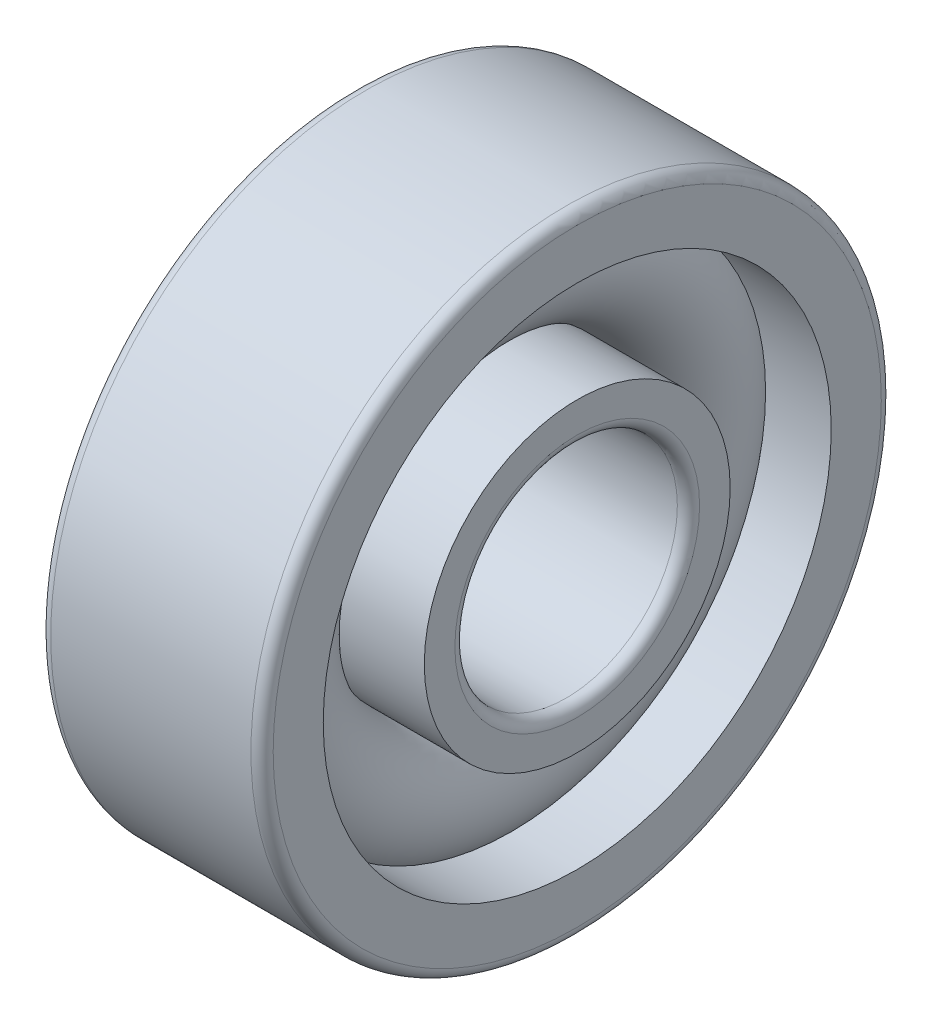
SolidWorks part; units mm, degrees
ref_plane "Plane1" through (0, 0, 0) normal (0, 0, 1) x (1, 0, 0)
ref_plane "Plane2" through (0, 0, 0) normal (0, 1, 0) x (1, 0, 0)
ref_plane "Plane3" through (0, 0, 0) normal (1, 0, 0) x (0, 0, -1)
sketch "Clipboard" plane through (0, 0, 0) normal (0, 0, 1) x (1, 0, 0)
  line L0 (-10, 0) -> (10, 0) construction
  line L1 (0, 0) -> (22.3471, -0.7804)
  line L2 (0, 0) -> (5.7465, 0.2007)
  line L3 (0, 0) -> (22.3471, -0.7804)
  line L4 (0, 0) -> (-22.3573, -0.3902)
sketch "CagSpiSke" plane through (0, 0, 0) normal (0, 0, 1) x (1, 0, 0)
  line L0 (0.4125, 5.475) -> (0.4125, 6.025)
  line L1 (0.4125, 6.025) -> (-0.4125, 6.025)
  line L2 (-0.4125, 6.025) -> (-0.4125, 5.475)
  line L3 (-0.4125, 5.475) -> (0.4125, 5.475)
  line L4 (-20.6375, 0) -> (20.6375, 0) construction
  line L5 (0, 0) -> (0, 23.7692) construction
revolve "CageSpine" add sketch "CagSpiSke" angle 0.001 about L4
ref_axis "Axis1" through (-50, 0, 0) along (1, 0, 0)
sketch "CagBalSke" plane through (0, 0, 0) normal (0, 0, 1) x (1, 0, 0)
  line L0 (-1.815, 5.75) -> (1.815, 5.75)
  line L1 (-1.905, 5.75) -> (1.905, 5.75) construction
  line L2 (-10, 0) -> (10, 0) construction
  line L3 (0, 0) -> (0, 24) construction
  arc A0 (1.815, 5.75) -> (-1.815, 5.75) centre (0, 5.75) cw
revolve "CageBall" [suppressed] add sketch "CagBalSke" angle 360 about L1 reverse direction yes
pattern_circular "CageBalls" [suppressed] count 2 every 180 about axis through (-50, 0, 0) along (1, 0, 0)
sketch "CagTrmODSke" plane through (0, 0, 0) normal (0, 0, 1) x (1, 0, 0)
  line L0 (1.816, 6.025) -> (1.816, 7.566)
  line L1 (1.816, 7.566) -> (-1.816, 7.566)
  line L2 (-1.816, 7.566) -> (-1.816, 6.025)
  line L3 (-1.816, 6.025) -> (1.816, 6.025)
  line L4 (-20.6375, 0) -> (20.6375, 0) construction
  line L5 (0, 0) -> (0, 25) construction
revolve "CageTrimOD" [suppressed] cut sketch "CagTrmODSke" angle 360 about L4 reverse direction yes
sketch "CagTrmIDSke" plane through (0, 0, 0) normal (0, 0, 1) x (1, 0, 0)
  line L0 (1.816, 3.936) -> (1.816, 5.475)
  line L1 (1.816, 5.475) -> (-1.816, 5.475)
  line L2 (-1.816, 5.475) -> (-1.816, 3.936)
  line L3 (-1.816, 3.936) -> (1.816, 3.936)
  line L4 (-20.6375, 0) -> (20.6375, 0) construction
  line L5 (0, 0) -> (0, 25) construction
revolve "CageTrimID" [suppressed] cut sketch "CagTrmIDSke" angle 360 about L4 reverse direction yes
sketch "BalSimSke" plane through (0, 0, 0) normal (0, 0, 1) x (1, 0, 0)
  line L0 (-10, 0) -> (10, 0) construction
  line L1 (-10, 5.75) -> (10, 5.75) construction
  line L2 (0, 0) -> (0, 23) construction
  circle A0 centre (0, 5.75) radius 1.65
revolve "BallsSimplified" add sketch "BalSimSke" angle 360 about L0
sketch "BalDetSke" plane through (0, 0, 0) normal (0, 0, 1) x (1, 0, 0)
  line L0 (-1.65, 5.75) -> (1.65, 5.75)
  line L1 (-1.905, 5.75) -> (1.905, 5.75) construction
  line L2 (0, 0) -> (0, 25) construction
  arc A0 (1.65, 5.75) -> (-1.65, 5.75) centre (0, 5.75) cw
revolve "BallDetailed" [suppressed] add sketch "BalDetSke" angle 360 about L1 reverse direction yes
sketch "InnRacSke" plane through (0, 0, 0) normal (0, 0, 1) x (1, 0, 0)
  line L0 (-1.1961, 4.65) -> (-3, 4.65)
  line L1 (-3, 4.65) -> (-3, 3.3)
  line L2 (-2.7, 3) -> (2.7, 3)
  line L3 (3, 3.3) -> (3, 4.125)
  line L4 (0, 4.125) -> (3, 4.125)
  line L5 (-20.6375, 0) -> (20.6375, 0) construction
  line L6 (0, 0) -> (0, 30) construction
  arc A0 (-3, 3.3) -> (-2.7, 3) centre (-2.7, 3.3) ccw
  arc A1 (2.7, 3) -> (3, 3.3) centre (2.7, 3.3) ccw
  arc A2 (0, 4.125) -> (-1.1961, 4.65) centre (0, 5.75) cw
revolve "InnerRace" add sketch "InnRacSke" angle 360 about L5 reverse direction yes
sketch "OutRacSke" plane through (0, 0, 0) normal (0, 0, 1) x (1, 0, 0)
  line L0 (0, 7.375) -> (-3, 7.375)
  line L1 (-3, 7.375) -> (-3, 8.2)
  line L2 (-2.7, 8.5) -> (2.7, 8.5)
  line L3 (3, 8.2) -> (3, 6.85)
  line L4 (3, 6.85) -> (1.1961, 6.85)
  line L5 (-20.6375, 0) -> (20.6375, 0) construction
  line L6 (0, 0) -> (0, 30) construction
  arc A0 (-3, 8.2) -> (-2.7, 8.5) centre (-2.7, 8.2) cw
  arc A1 (2.7, 8.5) -> (3, 8.2) centre (2.7, 8.2) cw
  arc A2 (1.1961, 6.85) -> (0, 7.375) centre (0, 5.75) ccw
revolve "OuterRace" add sketch "OutRacSke" angle 360 about L5 reverse direction yes
pattern_circular "BallsDetailed" [suppressed] count 2 every 180 about axis through (-50, 0, 0) along (1, 0, 0)
equation "\"BallCLRad@Clipboard\" = ( \"OD@OutRacSke\" + \"ID@InnRacSke\" ) / 4"
equation "\"BallCLRad@BalSimSke\" = \"BallCLRad@Clipboard\""
equation "\"BallCLRad@BalDetSke\" = \"BallCLRad@Clipboard\""
equation "\"BallCLRad@InnRacSke\" = \"BallCLRad@Clipboard\""
equation "\"BallCLRad@OutRacSke\" = \"BallCLRad@Clipboard\""
equation "\"Ball_diameter@InnRacSke\" = \"Ball_diameter@BalDetSke\" - 0.05"
equation "\"Ball_diameter@OutRacSke\" = \"Ball_diameter@BalDetSke\" - 0.05"
equation "\"Ball_diameter@BalSimSke\" = \"Ball_diameter@BalDetSke\""
equation "\"Width@OutRacSke\" = \"Width@InnRacSke\""
equation "\"Fillet_radius@OutRacSke\" = \"Fillet_radius@InnRacSke\""
equation "\"Max_count@Clipboard\" = int( 3.14159265 / atn(( \"Ball_diameter@BalDetSke\" / 2) / sqr( \"BallCLRad@Clipboard\"  *  \"BallCLRad@Clipboard\" - ( \"Ball_diameter@BalDetSke\" / 2) *  ( \"Ball_diameter@BalDetSke\" / 2))))"
equation "\"Max_count@Clipboard\" = ((sgn( \"Max_count@Clipboard\" - \"Count@Clipboard\" )-1)*( \"Max_count@Clipboard\" - \"Count@Clipboard\" ))/-2+ \"Count@Clipboard\""
equation "\"Count@BallsDetailed\" = int( \"Show_count@Clipboard\" ) "
equation "\"Count@BallsDetailed\" = ((sgn( \"Count@BallsDetailed\" - \"Max_count@Clipboard\" )-1)*( \"Count@BallsDetailed\" - \"Max_count@Clipboard\" ))/-2+ \"Max_count@Clipboard\""
equation "\"Count@BallsDetailed\" = ((sgn( \"Count@BallsDetailed\" - \"Min_count@Clipboard\" )+1)*( \"Count@BallsDetailed\" - \"Min_count@Clipboard\"))/2 +\"Min_count@Clipboard\""
equation "\"Angle@BallsDetailed\" = 360.0 / \"Max_count@Clipboard\""
equation "\"BallCLRad@CagBalSke\" = \"BallCLRad@Clipboard\""
equation "\"Count@CageBalls\" = \"Count@BallsDetailed\""
equation "\"Angle@CageBalls\" = \"Angle@BallsDetailed\""
equation "\"Angle@CageSpine\" =  \"Angle@CageBalls\" * ( \"Count@CageBalls\" -1 + int( \"Count@CageBalls\" / \"Max_count@Clipboard\" ) )  + 0.001 -  int( \"Count@CageBalls\" / \"Max_count@Clipboard\" ) * 0.001"
equation "\"Angle@CageSpine\" =  \"Angle@CageSpine\" * int( \"Min_count@Clipboard\" / 2) + int(1 / \"Min_count@Clipboard\")  * 0.001"
equation "\"CageWallOD@CagBalSke\" =  \"Ball_diameter@BalDetSke\" * 1.1"
equation "\"Thickness@CagSpiSke\" =  \"Ball_diameter@BalDetSke\" * 0.25"
equation "\"OD@CagTrmODSke\" = \"BallCLRad@Clipboard\" * 2 + \"CageWallOD@CagBalSke\" + 0.002"
equation "\"ID@CagTrmODSke\" = \"BallCLRad@Clipboard\" * 2 + \"Ball_diameter@BalDetSke\" / 6"
equation "\"OD@CagTrmIDSke\" = \"BallCLRad@Clipboard\" * 2 - \"Ball_diameter@BalDetSke\" / 6"
equation "\"ID@CagTrmIDSke\" = \"BallCLRad@Clipboard\" * 2 - \"CageWallOD@CagBalSke\" + 0.002"
equation "\"OD@CagSpiSke\" = \"ID@CagTrmODSke\""
equation "\"ID@CagSpiSke\" = \"OD@CagTrmIDSke\""
equation "\"Width@CagTrmODSke\" = \"CageWallOD@CagBalSke\" + 0.002"
equation "\"Width@CagTrmIDSke\" = \"CageWallOD@CagBalSke\" + 0.002"
